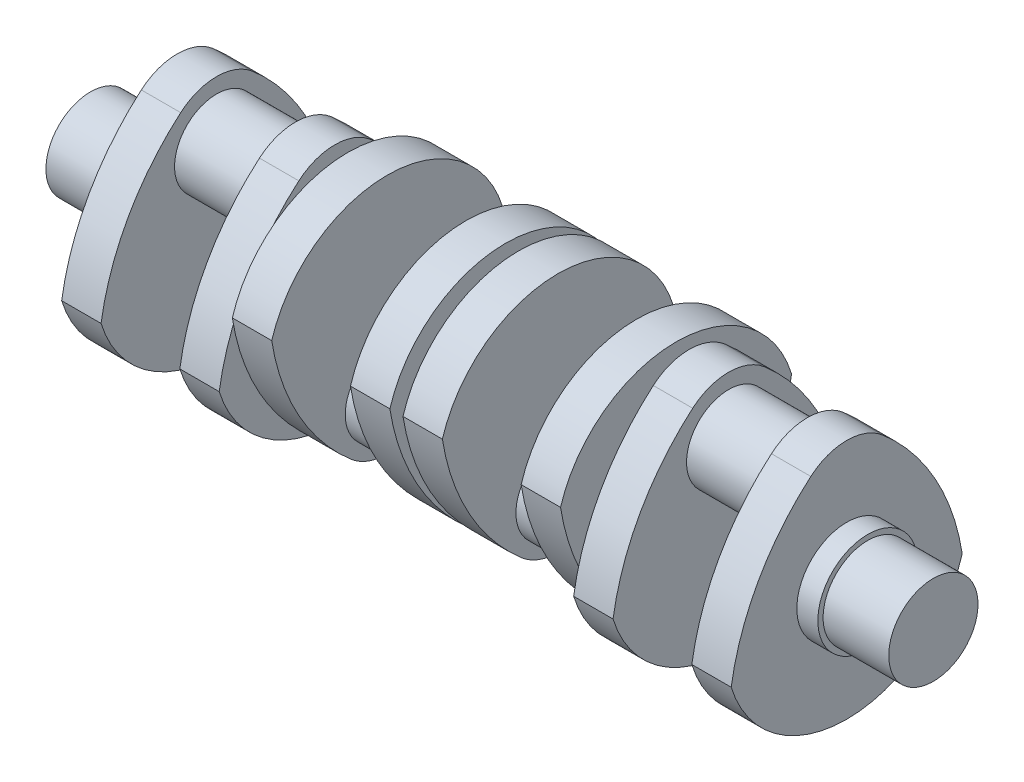
SolidWorks part; units mm, degrees
ref_plane "Front Plane" through (0, 0, 0) normal (0, 0, 1) x (1, 0, 0)
ref_plane "Top Plane" through (0, 0, 0) normal (0, 1, 0) x (1, 0, 0)
ref_plane "Right Plane" through (0, 0, 0) normal (1, 0, 0) x (0, 0, -1)
sketch "Sketch1" plane through (0, 0, 0) normal (1, 0, 0) x (0, 0, -1)
  circle A0 centre (0, 0) radius 482.6
  circle A1 centre (0, 0) radius 431.8
  dimension "D1" = 965.2
  dimension "D2" = 863.6
extrude "Boss-Extrude1" add sketch "Sketch1" against normal blind 635 contours A1
extrude "Boss-Extrude2" add sketch "Sketch1<3>" along normal blind 203.2 contours A0
sketch "Sketch1<3>" plane through (0, 0, 0) normal (1, 0, 0) x (0, 0, -1) same geometry as "Sketch1"
sketch "Sketch2" plane through (203.2, 0, 0) normal (1, 0, 0) x (0, 0, -1)
  arc A0 (-347.1696, 1039.9553) -> (347.1696, 1039.9553) centre (0, 635) cw
  arc A1 (-1117.6, -340.7768) -> (1117.6, -340.7768) centre (0, 0) ccw
  arc A2 (-347.1696, 1039.9553) -> (-1117.6, -340.7768) centre (1140.7001, -695.5675) ccw
  arc A3 (347.1696, 1039.9553) -> (1117.6, -340.7768) centre (-1140.7001, -695.5675) cw
  dimension "D3" = 1168.4
  dimension "D4" = 533.4
  dimension "D5" = 2286
  dimension "D6" = 2286
  dimension "D1" = 635
  dimension "D2" = 2235.2
extrude "Boss-Extrude3" add sketch "Sketch2" along normal blind 381
sketch "Sketch3" plane through (584.2, 0, 0) normal (1, 0, 0) x (0, 0, -1)
  circle A0 centre (0, 616.1972) radius 406.4
  dimension "D1" = 812.8
extrude "Boss-Extrude4" add sketch "Sketch3" along normal blind 381
mirror "Mirror2" about plane through (965.2, 616.1972, 0) normal (1, 0, 0) of "Boss-Extrude3", "Boss-Extrude4"
sketch "Sketch4" plane through (1727.2, 0, 0) normal (1, 0, 0) x (0, 0, -1)
  circle A0 centre (0, 0) radius 431.8
  dimension "D1" = 863.6
extrude "Boss-Extrude5" add sketch "Sketch4" along normal blind 127
sketch "Sketch5" plane through (1854.2, 0, 0) normal (1, 0, 0) x (0, 0, -1)
  circle A0 centre (0, 0) radius 431.8 construction
  arc A8 (-347.1696, -1039.9553) -> (347.1696, -1039.9553) centre (0, -635) ccw
  arc A9 (-1117.6, 340.7768) -> (-347.1696, -1039.9553) centre (1140.7001, 695.5675) ccw
  arc A10 (1117.6, 340.7768) -> (-1117.6, 340.7768) centre (0, 0) ccw
  arc A11 (347.1696, -1039.9553) -> (1117.6, 340.7768) centre (-1140.7001, 695.5675) ccw
  dimension "D1" = 533.4
  dimension "D2" = 2286
  dimension "D3" = 1168.4
  dimension "D4" = 347.1696
  dimension "D5" = 1117.6
extrude "Boss-Extrude6" add sketch "Sketch5" along normal blind 381
sketch "Sketch6" plane through (2235.2, 0, 0) normal (1, 0, 0) x (0, 0, -1)
  circle A0 centre (0, -635) radius 406.4
  dimension "D1" = 812.8
  dimension "D2" = 635
extrude "Boss-Extrude7" add sketch "Sketch6" along normal blind 762
sketch "Sketch7" plane through (2997.2, 0, 0) normal (1, 0, 0) x (0, 0, -1)
  arc A4 (-347.1696, -1039.9553) -> (347.1696, -1039.9553) centre (0, -635) ccw
  arc A5 (347.1696, -1039.9553) -> (1117.6, 340.7768) centre (-1140.7001, 695.5675) ccw
  arc A6 (1117.6, 340.7768) -> (-1117.6, 340.7768) centre (0, 0) ccw
  arc A7 (-1117.6, 340.7768) -> (-347.1696, -1039.9553) centre (1140.7001, 695.5675) ccw
  arc A8 (-347.1696, -1039.9553) -> (347.1696, -1039.9553) centre (0, -635) ccw
  arc A9 (347.1696, -1039.9553) -> (1117.6, 340.7768) centre (-1140.7001, 695.5675) ccw
  arc A10 (1117.6, 340.7768) -> (-1117.6, 340.7768) centre (0, 0) ccw
  arc A11 (-1117.6, 340.7768) -> (-347.1696, -1039.9553) centre (1140.7001, 695.5675) ccw
  dimension "D1" = 0
extrude "Boss-Extrude8" add sketch "Sketch7" along normal blind 381
sketch "Sketch8" plane through (3378.2, 0, 0) normal (1, 0, 0) x (0, 0, -1)
  circle A0 centre (0, 0) radius 431.8
  dimension "D1" = 863.6
extrude "Boss-Extrude9" add sketch "Sketch8" along normal blind 63.5
mirror "Mirror3" about plane through (3441.7, 0, 0) normal (1, 0, 0) of bodies 111
